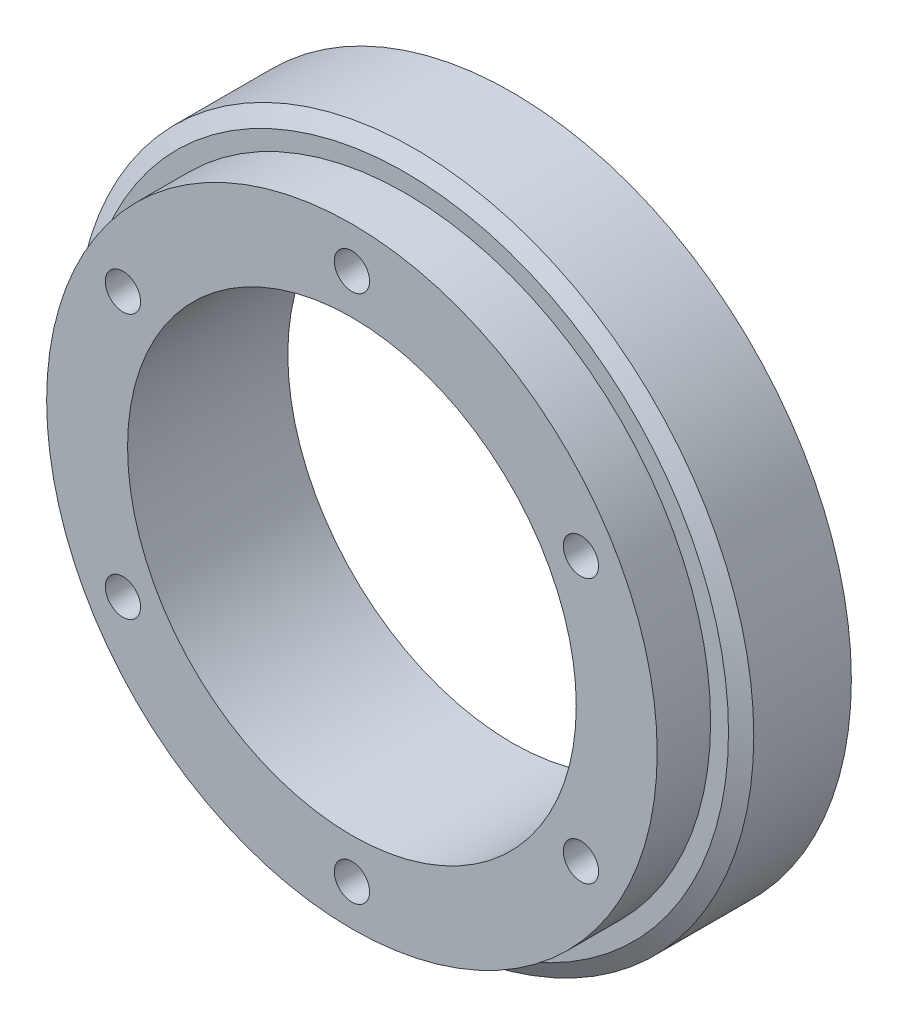
SolidWorks part; units mm, degrees
ref_plane "Front Plane" through (0, 0, 0) normal (0, 0, 1) x (1, 0, 0)
ref_plane "Top Plane" through (0, 0, 0) normal (0, 1, 0) x (1, 0, 0)
ref_plane "Right Plane" through (0, 0, 0) normal (1, 0, 0) x (0, 0, -1)
sketch "Sketch1" plane through (0, 0, 0) normal (1, 0, 0) x (0, 0, -1)
  line L0 (0, 31.75) -> (-9.134, 31.75)
  line L1 (-9.134, 31.75) -> (-10, 30.25)
  line L4 (-15, 0) -> (0, 0) construction
  line L9 (-15, 28.575) -> (-15, 21)
  line L10 (-15, 21) -> (0, 21)
  line L11 (0, 21) -> (0, 31.75)
  line L12 (-15, -21) -> (0, -21) construction
  line L13 (-15, -28.575) -> (-15, -21) construction
  line L14 (-10, -30.25) -> (-15, -28.575) construction
  line L15 (-9.134, -31.75) -> (-10, -30.25) construction
  line L16 (0, -31.75) -> (-9.134, -31.75) construction
  line L17 (0, -21) -> (0, -31.75) construction
  line L18 (-15, 28.575) -> (-10, 28.575)
  line L19 (-10, 28.575) -> (-10, 30.25)
  dimension "D1" = 63.5
  dimension "D2" = 3.175
  dimension "D3" = 30
  dimension "D4" = 42
  dimension "D5" = 10
  dimension "D6" = 15
  dimension "D7" = 1.5
revolve "Revolve1" add sketch "Sketch1" angle 360 about L4
sketch "Sketch2" plane through (0, 0, 0) normal (0, 0, -1) x (-1, 0, 0)
  circle A0 centre (0, 0) radius 24.75 construction
  point P3 (0, 24.75)
  dimension "D1" = 49.5
hole_wizard "M4x0.7 Tapped Hole1" positions "Sketch2" profile "Sketch3" tap size "M4x0.7" standard "ANSI Metric" end condition through all
sketch "Sketch3" plane through (0, 24.75, 0) normal (1, 0, 0) x (0, 1, 0)
  line L0 (0, 0) -> (0, 15)
  line L1 (0, 15) -> (1.65, 15)
  line L2 (1.65, 15) -> (1.65, 0)
  line L5 (1.65, 0) -> (0, 0)
  line L11 (0, -6.35) -> (0, 107.95) construction
  dimension "Thru Tap Drill Dia." = 3.3
  dimension "Thru Tap Drill Depth" = 15
cosmetic thread "Hole Thread1" parameters "D2"=4
pattern_circular "CirPattern1" count 6 over 360 about axis through (0, 0, 15) along (0, 0, 1) of "M4x0.7 Tapped Hole1"
cosmetic thread "Hole Thread2" parameters "D2"=4
cosmetic thread "Hole Thread3" parameters "D2"=4
cosmetic thread "Hole Thread4" parameters "D2"=4
cosmetic thread "Hole Thread5" parameters "D2"=4
cosmetic thread "Hole Thread6" parameters "D2"=4
